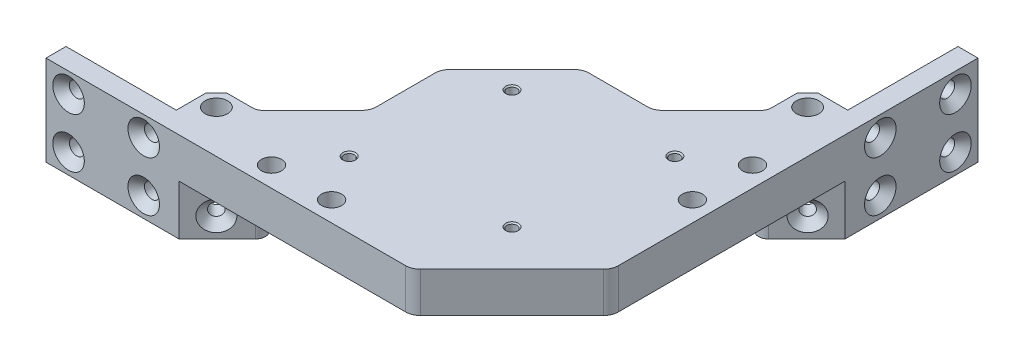
SolidWorks part; units mm, degrees
material "6061 合金"
ref_plane "前视基准面" through (0, 0, 0) normal (0, 0, 1) x (1, 0, 0)
ref_plane "上视基准面" through (0, 0, 0) normal (0, 1, 0) x (1, 0, 0)
ref_plane "右视基准面" through (0, 0, 0) normal (1, 0, 0) x (0, 0, -1)
other "Configuration Table"
sketch "草图1" plane through (0, 0, 0) normal (0, 1, 0) x (1, 0, 0)
  line L0 (0, 0) -> (0, 93)
  line L1 (0, 93) -> (-4, 93)
  line L2 (-4, 93) -> (-4, 71)
  line L3 (-4, 71) -> (-12, 71)
  line L4 (-12, 71) -> (-12, 62.9117)
  line L5 (-12, 62.9117) -> (-62.9117, 12)
  line L6 (-62.9117, 12) -> (-71, 12)
  line L7 (-71, 12) -> (-71, 4)
  line L8 (-71, 4) -> (-93, 4)
  line L9 (-93, 4) -> (-93, 0)
  line L10 (-93, 0) -> (0, 0)
  line L11 (0, 0) -> (-37.4558, 37.4558) construction
  line L12 (-81, 4) -> (-81, 23.207) construction
  circle A0 centre (-8.5, 67.5) radius 2.25
  circle A1 centre (-67.5, 8.5) radius 2.25
  point P15 (-8, 71)
  dimension "D7" = 3.5
  dimension "D10" = 4.5
  dimension "D1" = 93
  dimension "D2" = 45
  dimension "D3" = 72
  dimension "D4" = 22
  dimension "D5" = 10
  dimension "D6" = 4
  dimension "D8" = 3.5
  dimension "D9" = 8
extrude "凸台-拉伸1" add sketch "草图1" along normal blind 18
sketch "草图2" plane through (0, 0, -4) normal (0, 0, -1) x (-1, 0, 0)
  line L0 (81, 18) -> (81, 0) construction
  line L1 (71, 18) -> (93, 18) construction
  line L2 (71, 0) -> (93, 0) construction
  line L3 (71, 18) -> (71, 0) construction
  line L5 (73.5, 4) -> (88.5, 4) construction
  line L6 (73.5, 4) -> (73.5, 14) construction
  line L7 (73.5, 14) -> (88.5, 14) construction
  line L8 (88.5, 4) -> (88.5, 14) construction
  line L9 (73.5, 4) -> (88.5, 14) construction
  line L10 (73.5, 14) -> (88.5, 4) construction
  circle A0 centre (73.5, 14) radius 1.5
  circle A1 centre (88.5, 14) radius 1.5
  circle A2 centre (88.5, 4) radius 1.5
  circle A3 centre (73.5, 4) radius 1.5
  point P8 (81, 9)
  dimension "D4" = 3
  dimension "D1" = 10
  dimension "D2" = 15
  dimension "D3" = 10
extrude "切除-拉伸1" cut sketch "草图2" against normal through all
ref_plane "基准面1" through (0, 0, 0) normal (0.7071, 0, -0.7071) x (0, -1, 0)
mirror "镜向2" about plane through (0, 0, 0) normal (0.7071, 0, -0.7071) of "切除-拉伸1"
chamfer "倒角1" distance 1.65 angle 45 8 edges at (-90, 14, 0) (-90, 4, 0) (-75, 4, 0) (-75, 14, 0) (0, 14, -75) (0, 14, -90) (0, 4, -90) (0, 4, -75)
chamfer "倒角2" distance 2 angle 45 2 edges at (-71, 9, -12) (-12, 9, -71)
sketch "草图3" plane through (0, 0, 0) normal (0, -1, 0) x (1, 0, 0)
  line L0 (0, 0) -> (-66.4264, 0)
  line L1 (-93, 0) -> (0, 0) construction
  line L2 (-66.4264, 0) -> (0, -66.4264)
  line L3 (0, 0) -> (0, -93) construction
  line L4 (0, -66.4264) -> (0, 0)
  line L5 (-12, -62.9117) -> (-62.9117, -12) construction
  dimension "D1" = 6
extrude "切除-拉伸2" cut sketch "草图3" against normal blind 10
sketch "草图4" plane through (-40.5, 0, -40.5) normal (-0.7071, 0, -0.7071) x (-0.7071, 0, 0.7071)
  line L0 (-41.7193, 18) -> (-41.7193, 0) construction
  line L1 (-43.1335, 18) -> (-40.3051, 18) construction
  line L2 (-40.3051, 0) -> (-43.1335, 0) construction
  line L3 (41.7193, 0) -> (41.7193, 18) construction
  line L4 (43.1335, 0) -> (40.3051, 0) construction
  line L5 (40.3051, 18) -> (43.1335, 18) construction
  line L7 (41.7193, 4) -> (-41.7193, 4) construction
  circle A0 centre (-41.7193, 4) radius 1.25
  circle A1 centre (41.7193, 4) radius 1.25
  point P17 (-41.7193, 4)
  point P18 (41.7193, 4)
  dimension "D1" = 4
  dimension "D2" = 2.5
hole_wizard "M3 螺纹孔1" positions "草图7" profile "草图8" tap size "M3" standard "GB" end condition through all
sketch "草图7" plane through (-40.5, 0, -40.5) normal (-0.7071, 0, -0.7071) x (-0.7071, 0, 0.7071)
  point P0 (-41.7193, 4)
  point P3 (41.7193, 4)
sketch "草图8" plane through (-11, 4, -70) normal (0, 1, 0) x (-0.7071, 0, 0.7071)
  line L0 (0, 0) -> (0, 57.2756)
  line L1 (0, 57.2756) -> (1.25, 57.2756)
  line L2 (1.25, 57.2756) -> (1.25, 0.275)
  line L3 (1.25, 0.275) -> (1.525, 0)
  line L5 (1.525, 0) -> (0, 0)
  line L6 (-1.25, 0.275) -> (-1.525, 0) construction
  line L11 (0, -6.35) -> (0, 107.95) construction
  dimension "通孔螺纹孔钻头直径" = 2.5
  dimension "通孔螺纹孔钻头深度" = 57.2756
  dimension "近端锥形沉头孔直径" = 3.05
  dimension "近端锥形沉头孔角度" = 90
cosmetic thread "孔螺纹线1" parameters "D2"=3
cosmetic thread "孔螺纹线2" parameters "D2"=3
chamfer "倒角3" distance 1.65 angle 45 2 edges at (-4.5971, 4, -61.8293) (-63.5971, 4, -2.8293)
sketch "草图9" plane through (0, 18, 0) normal (0, 1, 0) x (1, 0, 0)
  line L0 (-71, 4) -> (0, 4) construction
  line L1 (0, 0) -> (0, 93) construction
  line L2 (-4, 71) -> (-4, 0) construction
  line L3 (-93, 0) -> (0, 0) construction
  line L4 (0, 0) -> (-37.4558, 37.4558) construction
  line L5 (-12, 62.9117) -> (-62.9117, 12) construction
  circle A0 centre (-52, 4) radius 2
  circle A1 centre (-40, 4) radius 2
  circle A4 centre (-4, 40) radius 2
  circle A5 centre (-4, 52) radius 2
  dimension "D1" = 52
  dimension "D2" = 12
  dimension "D3" = 4
extrude "切除-拉伸3" cut sketch "草图9" against normal through all
chamfer "倒角4" distance 20 angle 45 1 edges at (0, 14, 0)
fillet "圆角1" radius 2 2 edges at (-62.9117, 9, -12) (-12, 9, -62.9117)
sketch "草图10" plane through (0, 10, 0) normal (0, -1, 0) x (1, 0, 0)
  line L0 (-58.9264, -7.5) -> (-16.7426, -7.5)
  line L1 (-16.7426, -7.5) -> (-7.5, -16.7426)
  line L2 (-7.5, -16.7426) -> (-7.5, -58.9264)
  line L3 (-7.5, -58.9264) -> (-58.9264, -7.5)
  line L4 (0, -20) -> (-20, 0) construction
  line L5 (-66.4264, 0) -> (0, -66.4264) construction
  line L6 (0, -66.4264) -> (0, -20) construction
  line L7 (-20, 0) -> (-66.4264, 0) construction
  dimension "D1" = 3
  dimension "D2" = 0
  dimension "D3" = 7.5
  dimension "D4" = 7.5
extrude "切除-拉伸4" cut sketch "草图10" against normal blind 4
fillet "圆角2" radius 2 4 edges at (-7.5, 12, -16.7426) (-16.7426, 12, -7.5) (-7.5, 12, -58.9264) (-58.9264, 12, -7.5)
sketch "草图11" plane through (0, 18, 0) normal (0, 1, 0) x (1, 0, 0)
  line L0 (-51.598, 23.3137) -> (-51.598, 37.4558)
  line L1 (-12.5858, 62.3259) -> (-62.3259, 12.5858) construction
  line L2 (-51.598, 37.4558) -> (-37.4558, 51.598)
  line L3 (-37.4558, 51.598) -> (-23.3137, 51.598)
  line L4 (-10, 10) -> (-37.4558, 37.4558) construction
  line L5 (-20, 0) -> (0, 20) construction
  line L6 (-44.5269, 44.5269) -> (-37.4558, 37.4558) construction
  line L7 (-23.3137, 51.598) -> (-51.598, 23.3137)
  dimension "D1" = 20
  dimension "D2" = 45
  dimension "D3" = 10
extrude "凸台-拉伸2" add sketch "草图11" against normal blind 4
fillet "圆角3" radius 3 4 edges at (-51.598, 16, -23.3137) (-51.598, 16, -37.4558) (-37.4558, 16, -51.598) (-23.3137, 16, -51.598)
sketch "草图12" plane through (0, 14, 0) normal (0, -1, 0) x (1, 0, 0)
  line L0 (-48.598, -30.5563) -> (-48.598, -36.2132)
  line L1 (-48.598, -36.2132) -> (-36.2132, -48.598)
  line L2 (-36.2132, -48.598) -> (-30.5563, -48.598)
  line L3 (-30.5563, -48.598) -> (-48.598, -30.5563)
  line L4 (-51.598, -36.2132) -> (-51.598, -24.5563) construction
  line L5 (-38.3345, -50.7193) -> (-50.7193, -38.3345) construction
  line L6 (-12.5858, -62.3259) -> (-62.3259, -12.5858) construction
  line L7 (-24.5563, -51.598) -> (-36.2132, -51.598) construction
  dimension "D1" = 3
  dimension "D2" = 3
  dimension "D3" = 3
  dimension "D4" = 3
fillet "圆角4" radius 3 2 edges at (0, 14, -20) (-20, 14, 0)
sketch "草图13" plane through (0, 18, 0) normal (0, 1, 0) x (1, 0, 0)
  line L0 (-44.5269, 44.5269) -> (-10, 10) construction
  line L1 (-38.3345, 50.7193) -> (-50.7193, 38.3345) construction
  line L2 (-19.1213, 0.8787) -> (-0.8787, 19.1213) construction
  line L4 (-13.2728, 45.7714) -> (-45.7714, 13.2728) construction
  circle A0 centre (-17.3104, 17.3104) radius 1.25 construction
  circle A1 centre (-40.9914, 40.9914) radius 1.25 construction
  point P6 (-17.3104, 17.3104)
  point P8 (-40.9914, 40.9914)
  point P11 (-13.2728, 45.7714)
  point P12 (-45.7714, 13.2728)
  point P32 (-29.5221, 29.5221)
  dimension "D1" = 33.49
  dimension "D2" = 2.5
  dimension "D3" = 5
  dimension "D5" = 17.27
  dimension "D4" = 45.96
hole_wizard "M2.5 螺纹孔1" positions "草图13" profile "草图14" tap size "M2.5" standard "GB" end condition through all
sketch "草图14" plane through (-45.7714, 18, -13.2728) normal (1, 0, 0) x (0, 0, 1)
  line L0 (0, 0) -> (0, 18)
  line L1 (0, 18) -> (1.025, 18)
  line L2 (1.025, 18) -> (1.025, 0.25)
  line L3 (1.025, 0.25) -> (1.275, 0)
  line L5 (1.275, 0) -> (0, 0)
  line L6 (-1.025, 0.25) -> (-1.275, 0) construction
  line L11 (0, -6.35) -> (0, 107.95) construction
  dimension "通孔螺纹孔钻头直径" = 2.05
  dimension "通孔螺纹孔钻头深度" = 18
  dimension "近端锥形沉头孔直径" = 2.55
  dimension "近端锥形沉头孔角度" = 90
cosmetic thread "孔螺纹线4" parameters "D2"=2.5
cosmetic thread "孔螺纹线5" parameters "D2"=2.5
cosmetic thread "孔螺纹线9" parameters "D2"=2.5
cosmetic thread "孔螺纹线11" parameters "D2"=2.5
sketch "草图15" plane through (-33.2132, 0, -33.2132) normal (0.7071, 0, 0.7071) x (0.7071, 0, -0.7071)
  line L0 (-46.9706, 0) -> (46.9706, 0) construction
  line L1 (-34.2193, 0) -> (34.2193, 0)
  line L2 (-34.2193, 0) -> (-34.2193, 10)
  line L3 (-34.2193, 10) -> (34.2193, 10)
  line L4 (34.2193, 0) -> (34.2193, 10)
  line L5 (31.5355, 10) -> (46.9706, 10) construction
  circle A0 centre (-41.7193, 4) radius 2.9 construction
  circle A1 centre (41.7193, 4) radius 2.9 construction
  dimension "D1" = 7.5
  dimension "D2" = 7.5
extrude "切除-拉伸5" cut sketch "草图15" against normal through all
fillet "圆角5" radius 2 4 edges at (-9.0165, 5, -57.4099) (-13.2591, 5, -61.6525) (-61.6525, 5, -13.2591) (-57.4099, 5, -9.0165)
